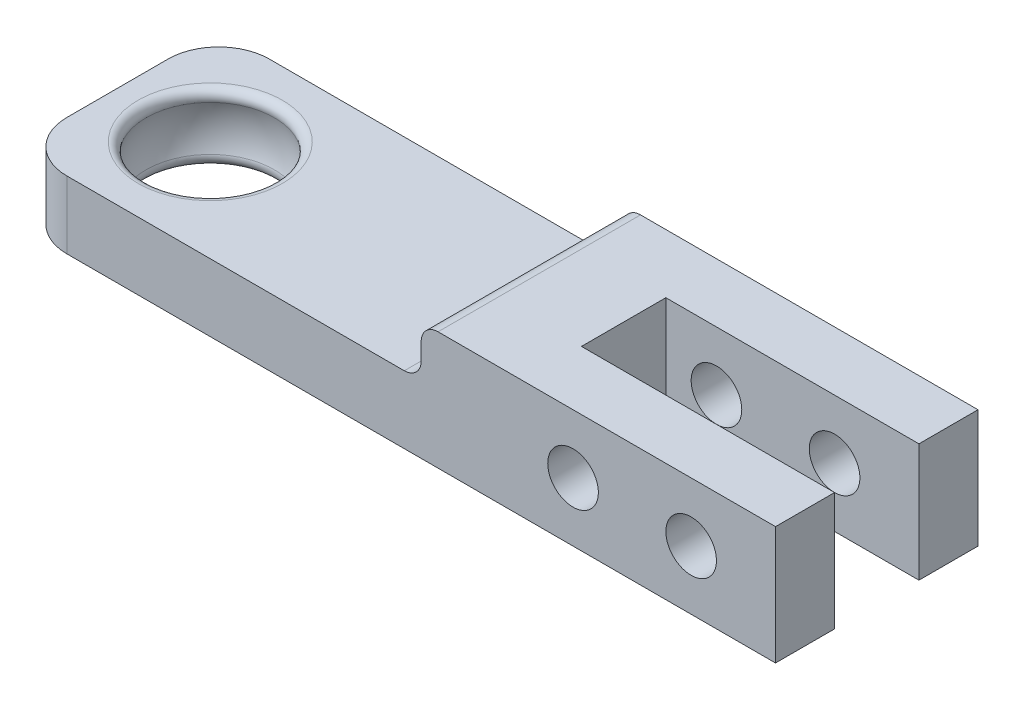
SolidWorks part; units mm, degrees
ref_plane "Front Plane" through (0, 0, 0) normal (0, 0, 1) x (1, 0, 0)
ref_plane "Top Plane" through (0, 0, 0) normal (0, 1, 0) x (1, 0, 0)
ref_plane "Right Plane" through (0, 0, 0) normal (1, 0, 0) x (0, 0, -1)
sketch "Sketch1" plane through (0, 0, 0) normal (0, 1, 0) x (1, 0, 0)
  line L1 (-22.5, 6) -> (22.5, 6)
  line L2 (-22.5, 6) -> (-22.5, -6)
  line L3 (-22.5, -6) -> (22.5, -6)
  line L4 (22.5, 6) -> (22.5, -6)
  line L5 (-22.5, 6) -> (22.5, -6) construction
  line L6 (-22.5, -6) -> (22.5, 6) construction
  point P0 (0, 0)
  dimension "D1" = 12
  dimension "D2" = 45
extrude "Boss-Extrude1" add sketch "Sketch1" along normal mid plane 4
sketch "Sketch2" plane through (0, 0, 0) normal (0, 0, 1) x (1, 0, 0)
  line L0 (-17, 2) -> (-17, -2)
  line L1 (-22.5, 2) -> (22.5, 2) construction
  line L2 (-22.5, -2) -> (22.5, -2) construction
  line L3 (-17, 2) -> (-20.5, 2)
  line L4 (-17, -2) -> (-20.5, -2)
  arc A0 (-20.5, 2) -> (-20.5, -2) centre (-17, 0) ccw
  dimension "D1" = 17
  dimension "D2" = 3.5
  dimension "D3" = 4
revolve "Cut-Revolve2" cut sketch "Sketch2" angle 360 about L0
fillet "Fillet1" radius 3 2 edges at (-22.5, 0, -6) (-22.5, 0, 6)
fillet "Fillet15" radius 0.5 2 edges at (-17, 2, 3.5) (-17, -2, 3.5)
sketch "Sketch11" plane through (22.5, 0, 0) normal (1, 0, 0) x (0, 0, -1)
  line L0 (-6, -2) -> (6, -2) construction
  line L1 (-2.5, 2) -> (2.5, 2)
  line L2 (-2.5, 2) -> (-2.5, -2)
  line L3 (-2.5, -2) -> (2.5, -2)
  line L4 (2.5, 2) -> (2.5, -2)
  line L5 (-2.5, 2) -> (2.5, -2) construction
  line L6 (-2.5, -2) -> (2.5, 2) construction
  point P0 (0, 0)
  dimension "D1" = 5
extrude "Cut-Extrude2" cut sketch "Sketch11" against normal blind 15 and the other way through all
sketch "Sketch13" plane through (0, 2, 0) normal (0, 1, 0) x (1, 0, 0)
  line L0 (22.5, 6) -> (-19.5, 6) construction
  line L1 (22.5, 2.5) -> (7.5, 2.5)
  line L2 (22.5, 2.5) -> (22.5, 6)
  line L3 (22.5, 6) -> (1.5, 6)
  line L4 (1.5, 2.5) -> (1.5, 6)
  line L7 (1.5, 2.5) -> (1.5, -2.5)
  line L9 (7.5, 2.5) -> (7.5, -2.5)
  line L10 (7.5, -2.5) -> (22.5, -2.5)
  line L11 (1.5, -2.5) -> (1.5, -6)
  line L12 (1.5, -6) -> (22.5, -6)
  line L13 (22.5, -2.5) -> (22.5, -6)
extrude "Boss-Extrude3" add sketch "Sketch13" along normal blind 3
sketch "Sketch14" plane through (0, 0, -6) normal (0, 0, -1) x (-1, 0, 0)
  line L0 (-22.5, 5) -> (-22.5, -2) construction
  circle A0 centre (-17.5, 1.5) radius 1.5
  circle A1 centre (-10.5, 1.5) radius 1.5
  dimension "D1" = 3
  dimension "D2" = 3
  dimension "D3" = 7
  dimension "D4" = 5
extrude "Cut-Extrude4" cut sketch "Sketch14" against normal through all
fillet "Fillet17" radius 1 2 edges at (1.5, 2, 0) (1.5, 5, 0)
